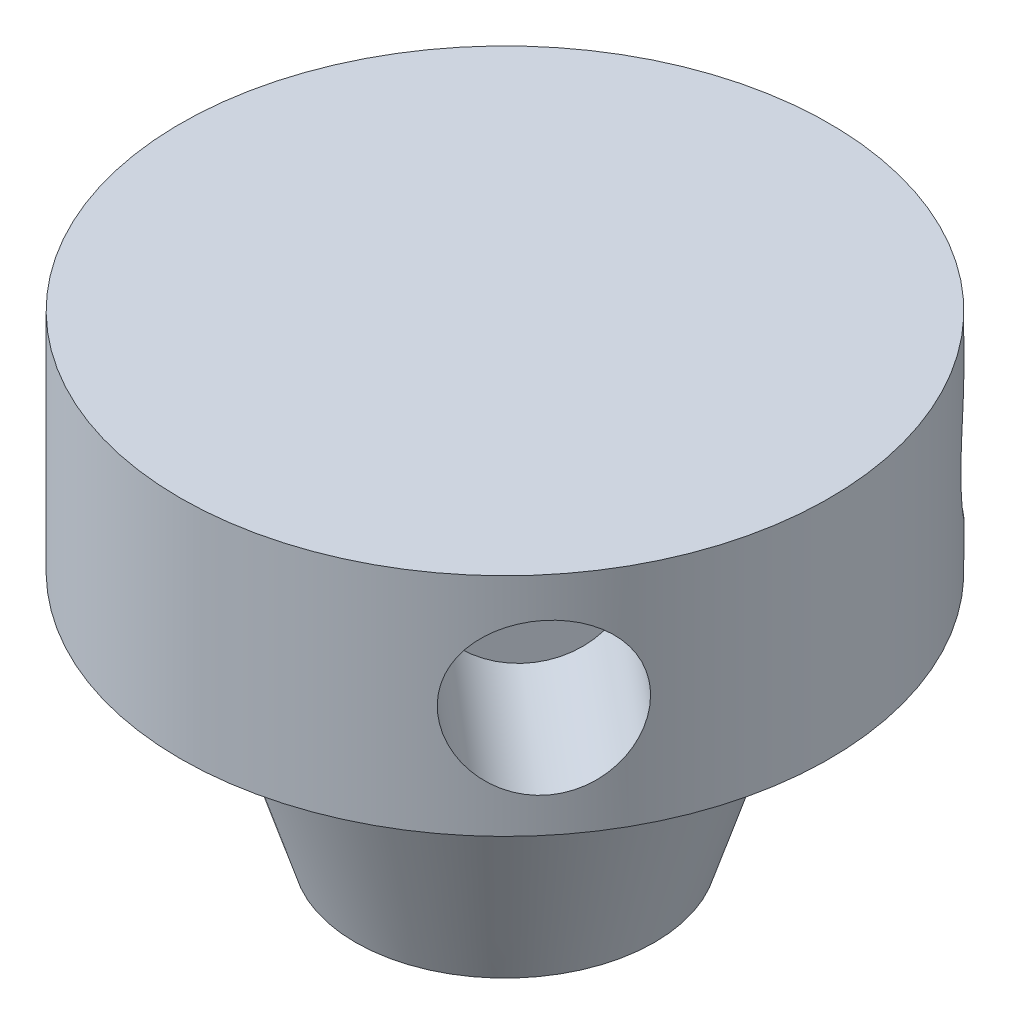
SolidWorks part; units mm, degrees
ref_plane "Спереди" through (0, 0, 0) normal (0, 0, 1) x (1, 0, 0)
ref_plane "Сверху" through (0, 0, 0) normal (0, 1, 0) x (1, 0, 0)
ref_plane "Справа" through (0, 0, 0) normal (1, 0, 0) x (0, 0, -1)
sketch "Эскиз1" plane through (0, 0, 0) normal (0, 0, 1) x (1, 0, 0)
  line L0 (0, 55.2693) -> (0, -51.4576) construction
  line L1 (0, 0) -> (13.833, 0)
  line L2 (13.833, 0) -> (21.0933, 22.7793)
  line L3 (21.0933, 22.7793) -> (30, 22.7793)
  line L4 (30, 22.7793) -> (30, 43.6527)
  line L5 (30, 43.6527) -> (0, 43.6527)
  line L6 (0, 0) -> (0, 43.6527)
revolve "Повернуть1" add sketch "Эскиз1" angle 360 about L0
ref_plane "Плоскость1" through (-30, 0, 0) normal (-1, 0, 0) x (0, 1, 0)
ref_plane "Плоскость2" through (-15, 0, -25.9808) normal (-0.5, 0, -0.866) x (0, 1, 0)
ref_plane "Плоскость3" through (18.4698, 0, -23.6403) normal (0.6157, 0, -0.788) x (0, 1, 0)
ref_plane "Плоскость4" through (22.9813, 0, 19.2836) normal (0.766, 0, 0.6428) x (0, 1, 0)
sketch "Эскиз2" plane through (-30, 0, 0) normal (-1, 0, 0) x (0, 1, 0)
  line L0 (0, 0) -> (111.3593, 0) construction
  circle A0 centre (33, 0) radius 7
extrude "Вырез-Вытянуть1" cut sketch "Эскиз2" against normal blind 15
sketch "Эскиз3" plane through (-15, 0, -25.9808) normal (-0.5, 0, -0.866) x (0, 1, 0)
  line L0 (0, 0) -> (46.7529, 0) construction
  circle A0 centre (33, 0) radius 7
extrude "Вырез-Вытянуть2" cut sketch "Эскиз3" against normal blind 15
sketch "Эскиз4" plane through (18.4698, 0, -23.6403) normal (0.6157, 0, -0.788) x (0, 1, 0)
  line L0 (0, 0) -> (43.6527, 0) construction
  line L1 (43.6527, -30) -> (43.6527, 30) construction
  circle A0 centre (33, 0) radius 7
extrude "Вырез-Вытянуть3" cut sketch "Эскиз4" against normal blind 15
sketch "Эскиз5" plane through (22.9813, 0, 19.2836) normal (0.766, 0, 0.6428) x (0, 1, 0)
  line L0 (0, 0) -> (43.6527, 0) construction
  line L1 (43.6527, -30) -> (43.6527, 30) construction
  circle A0 centre (33, 0) radius 7
extrude "Вырез-Вытянуть4" cut sketch "Эскиз5" against normal blind 15
